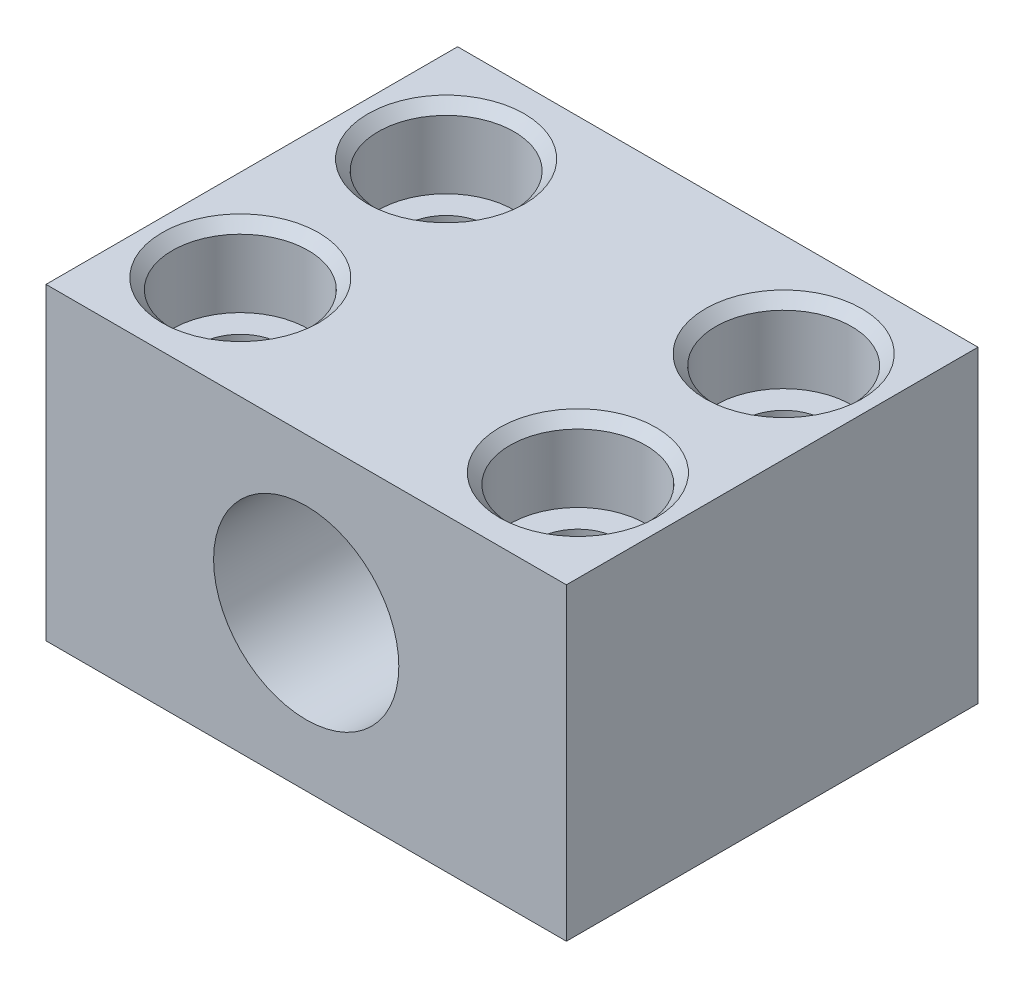
SolidWorks part; units mm, degrees
material "Brass"
ref_plane "Front Plane" through (0, 0, 0) normal (0, 0, 1) x (1, 0, 0)
ref_plane "Top Plane" through (0, 0, 0) normal (0, 1, 0) x (1, 0, 0)
ref_plane "Right Plane" through (0, 0, 0) normal (1, 0, 0) x (0, 0, -1)
sketch "Sketch1" plane through (0, 0, 0) normal (0, 0, 1) x (1, 0, 0)
  circle A0 centre (0, 0) radius 5.715
  circle A1 centre (0, 0) radius 18.669
  dimension "D3" = 11.43
  dimension "D1" = 37.338
extrude "nut-body-extrude" add sketch "Sketch1" along normal blind 25.4
sketch "Sketch2" plane through (0, 0, 0) normal (0, 0, 1) x (1, 0, 0)
  line L0 (0, 9.525) -> (0, 34.8179) construction
  line L1 (9.525, 0) -> (42.4926, 0) construction
  line L3 (-16.0563, 9.525) -> (16.0563, 9.525)
  line L4 (-16.0563, 9.525) -> (-16.0563, -9.525)
  line L5 (-16.0563, -9.525) -> (16.0563, -9.525)
  line L6 (16.0563, 9.525) -> (16.0563, -9.525)
  circle A1 centre (0, 0) radius 18.669
  circle A2 centre (0, 0) radius 18.669
  point P8 (-16.0563, 0)
  point P9 (0, 9.525)
  dimension "D1" = 19.05
  dimension "D2" = 0
extrude "nut-trim-cut-extrude" cut sketch "Sketch2" along normal through all contours L3 A2 | L5 A2 | L6 A2 | L4 A2 region at (0, 13.2722, 0) region at (-17.1079, 0, 0) region at (17.1079, 0, 0) region at (0, -13.2722, 0)
hole_wizard "CBORE for #10 Socket Head Cap Screw1" positions "Sketch5" profile "Sketch4" counterbore size "#10" standard "ANSI Inch" end condition through all
sketch "Sketch5" plane through (0, 9.525, 0) normal (0, 1, 0) x (1, 0, 0)
  line L0 (10.414, -6.35) -> (10.414, -19.05) construction
  line L1 (10.414, -19.05) -> (-10.414, -19.05) construction
  line L2 (-10.414, -19.05) -> (-10.414, -6.35) construction
  line L3 (-10.414, -6.35) -> (10.414, -6.35) construction
  line L4 (0, 0) -> (0, -12.7) construction
  line L5 (0, -12.7) -> (16.0563, -12.7) construction
  line L6 (16.0563, -25.4) -> (16.0563, 0) construction
  line L7 (-5.715, 0) -> (-5.715, -25.4) construction
  line L8 (-5.715, 0) -> (-5.715, -25.4) construction
  line L9 (5.715, 0) -> (5.715, -25.4) construction
  point P0 (10.414, -6.35)
  point P2 (10.414, -19.05)
  point P4 (-10.414, -19.05)
  point P6 (-10.414, -6.35)
  point P29 (10.414, -12.7)
  point P43 (0, -6.35)
  dimension "D1" = 20.828
  dimension "D2" = 12.7
sketch "Sketch4" plane through (10.414, 9.525, 6.35) normal (1, 0, 0) x (0, 0, 1)
  line L0 (0, 0) -> (0, 19.05)
  line L1 (0, 19.05) -> (2.5527, 19.05)
  line L3 (2.5527, 19.05) -> (2.5527, 4.826)
  line L4 (4.191, 4.826) -> (2.5527, 4.826)
  line L5 (4.191, 4.826) -> (4.191, 0.635)
  line L6 (4.191, 0.635) -> (4.826, 0)
  line L7 (4.826, 0) -> (0, 0)
  line L8 (-4.191, 0.635) -> (-4.826, 0) construction
  line L11 (0, -6.35) -> (0, 107.95) construction
  dimension "Thru Hole Dia." = 5.1054
  dimension "Thru Hole Depth" = 19.05
  dimension "C'Bore Dia." = 8.382
  dimension "C'Bore Depth" = 4.826
  dimension "Near C'Sink Dia." = 9.652
  dimension "Near C'Sink Angle" = 90
equation "\"dovetail-angle\" = 55"
equation "\"dovetail-stock-width\" = 5"
equation "\"dovetail-stock-height\" = 1.25"
equation "\"dovetail-depth\" = 0.5 * \"dovetail-stock-height\""
equation "\"dovetail-throat-width\" = \"dovetail-stock-width\" - (2 * \"dovetail-depth\")"
equation "\"delta-x\" = 6"
equation "\"delta-y\" = 3"
equation "\"gib-thickness\" = 0.25"
equation "\"x-slide-length\" = \"dovetail-stock-width\" + \"delta-x\""
equation "\"y-slide-length\" = \"dovetail-stock-width\" + \"delta-y\""
equation "\"dog-point-diam\" = .149"
equation "\"dog-point-length\" = .067"
equation "\"dovetail-double-height\" = 2 * \"dovetail-depth\" + 0.5"
equation "\"acme-major-diam\" = .5"
equation "\"acme-pitch-diam\" = 0.45"
equation "\"acme-minor-diam\" = 0.4"
equation "\"acme-nut-od\" = 1.47"
equation "\"acme-nut-length\" = 1"
equation "\"D3@Sketch1\"=\"acme-pitch-diam\""
equation "\"D1@Sketch1\"=\"acme-nut-od\""
equation "\"D1@nut-body-extrude\"=\"acme-nut-length\""
equation "\"acme-nut-trim-height\" = .75"
equation "\"D1@Sketch2\"=\"acme-nut-trim-height\""
equation "\"screw-bearing-od\" = 0.5"
equation "\"screw-bearing-length\" = .25"
equation "\"screw-bearing-id\" = .375"
equation "\"end-plate-thickness\" = \"screw-bearing-length\""
equation "\"screw-add-length\" = 2 * \"end-plate-thickness\" + 1 + 0.5"
equation "\"x-screw-length\" = \"x-slide-length\" + \"screw-add-length\""
equation "\"y-screw-length\" = \"y-slide-length\" + \"screw-add-length\""
equation "\"acme-nut-mount-hole-space-horz\" = 0.82"
equation "\"acme-nut-mount-hole-space-vert\" = 0.5 * \"acme-nut-length\""
equation "\"D2@Sketch5\"=\"acme-nut-mount-hole-space-vert\""
equation "\"D1@Sketch5\"=\"acme-nut-mount-hole-space-horz\""
